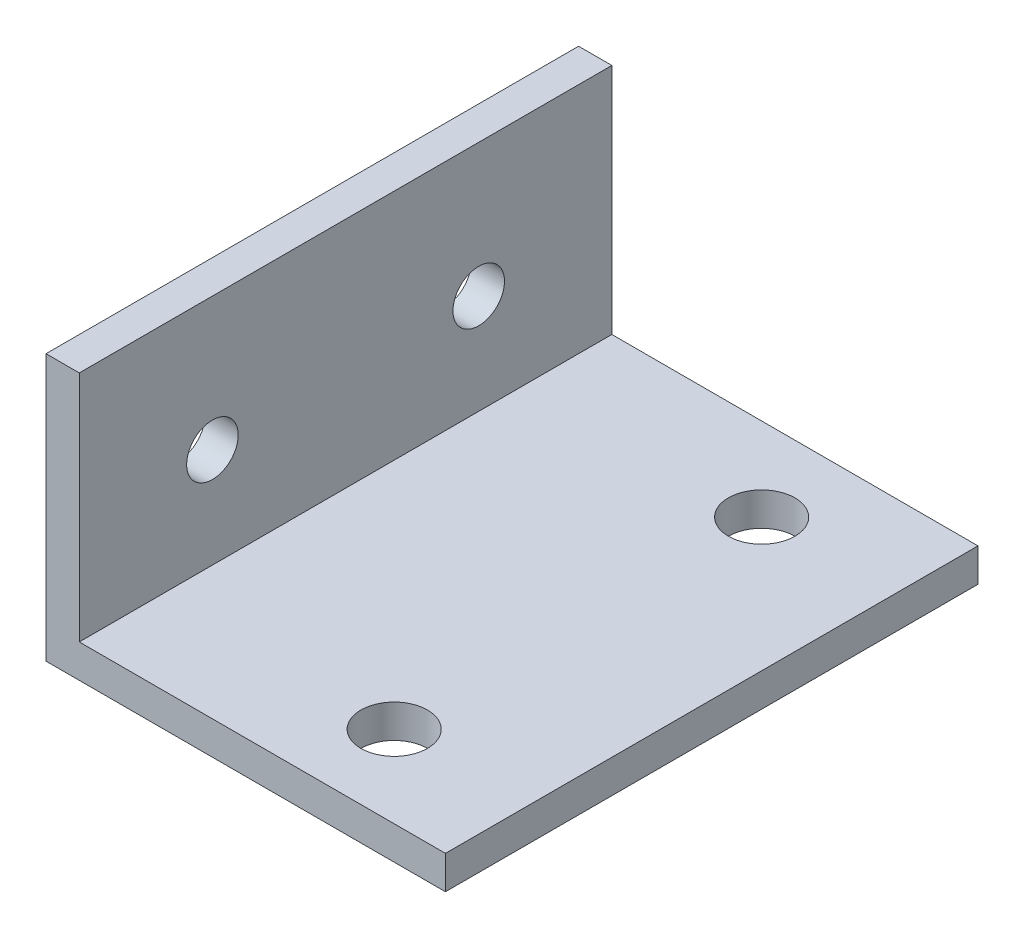
SolidWorks part; units mm, degrees
ref_plane "Front Plane" through (0, 0, 0) normal (0, 0, 1) x (1, 0, 0)
ref_plane "Top Plane" through (0, 0, 0) normal (0, 1, 0) x (1, 0, 0)
ref_plane "Right Plane" through (0, 0, 0) normal (1, 0, 0) x (0, 0, -1)
sketch "Sketch1" plane through (0, 0, 0) normal (0, 0, 1) x (1, 0, 0)
  line L0 (-8.1265, 19.7682) -> (-8.1265, -5.6318)
  line L1 (-8.1265, -5.6318) -> (29.9735, -5.6318)
  line L2 (29.9735, -5.6318) -> (29.9735, -2.4568)
  line L3 (29.9735, -2.4568) -> (-4.9515, -2.4568)
  line L4 (-4.9515, -2.4568) -> (-4.9515, 19.7682)
  line L5 (-4.9515, 19.7682) -> (-8.1265, 19.7682)
  dimension "D1" = 3.175
  dimension "D2" = 3.175
  dimension "D3" = 38.1
  dimension "D4" = 25.4
extrude "Boss-Extrude1" add sketch "Sketch1" along normal mid plane 50.8
hole_wizard "1/4 (0.25) Diameter Hole1" positions "Sketch5" profile "Sketch4" hole size "1/4" standard "ANSI Inch"
sketch "Sketch5" plane through (0, -2.4568, 0) normal (0, 1, 0) x (1, 0, 0)
  line L0 (29.9735, -25.4) -> (29.9735, 25.4) construction
  line L1 (29.9735, 25.4) -> (-4.9515, 25.4) construction
  point P0 (17.2735, 17.4625)
  point P13 (17.2735, -17.5895)
  dimension "D1" = 12.7
  dimension "D2" = 7.9375
  dimension "D3" = 2
sketch "Sketch4" plane through (17.2735, -2.4568, -17.4625) normal (1, 0, 0) x (0, 0, 1)
  line L0 (0, 0) -> (0, 19.4337)
  line L1 (0, 19.4337) -> (3.175, 17.526)
  line L2 (3.175, 17.526) -> (3.175, 0)
  line L5 (3.175, 0) -> (0, 0)
  line L10 (0, 19.4337) -> (-3.175, 17.526) construction
  line L11 (0, -6.35) -> (0, 107.95) construction
  dimension "Hole Dia." = 6.35
  dimension "Hole Depth" = 17.526
  dimension "Drill Angle" = 118
hole_wizard "#10 (0.1935) Diameter Hole1" positions "Sketch7" profile "Sketch6" hole size "#10" standard "ANSI Inch"
sketch "Sketch7" plane through (-4.9515, 0, 0) normal (1, 0, 0) x (0, 0, -1)
  line L0 (25.4, -2.4568) -> (25.4, 19.7682) construction
  line L1 (-25.4, 19.7682) -> (25.4, 19.7682) construction
  point P0 (12.7, 7.0682)
  point P20 (-12.7, 7.0682)
  dimension "D1" = 12.7
  dimension "D2" = 12.7
  dimension "D3" = 2
sketch "Sketch6" plane through (-4.9515, 7.0682, -12.7) normal (0, 1, 0) x (0, 0, -1)
  line L0 (0, 0) -> (0, 19.0026)
  line L1 (0, 19.0026) -> (2.4574, 17.526)
  line L2 (2.4574, 17.526) -> (2.4574, 0)
  line L5 (2.4574, 0) -> (0, 0)
  line L10 (0, 19.0026) -> (-2.4575, 17.526) construction
  line L11 (0, -6.35) -> (0, 107.95) construction
  dimension "Hole Dia." = 4.9149
  dimension "Hole Depth" = 17.526
  dimension "Drill Angle" = 118
